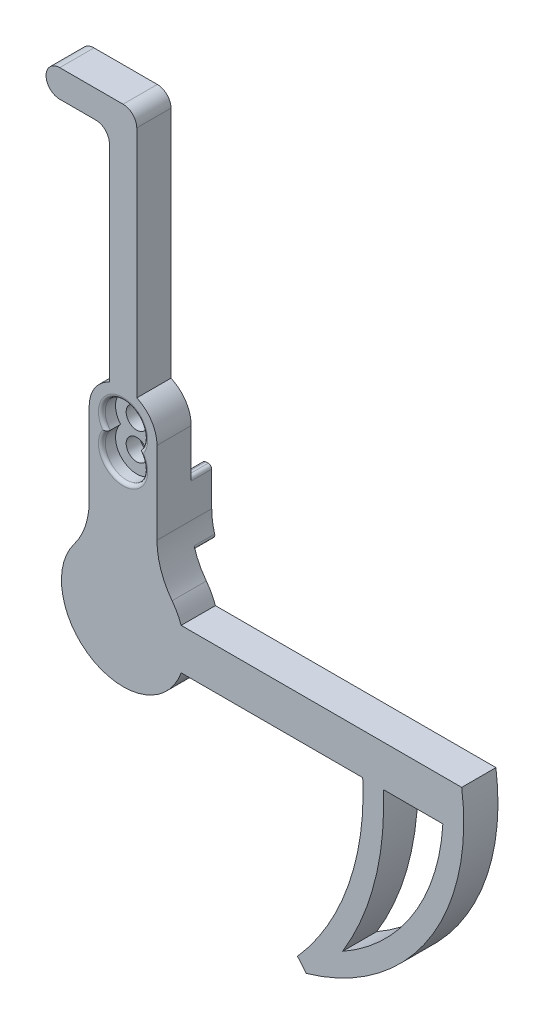
SolidWorks part; units mm, degrees
material "PLA"
ref_plane "Front Plane" through (0, 0, 0) normal (0, 0, 1) x (1, 0, 0)
ref_plane "Top Plane" through (0, 0, 0) normal (0, 1, 0) x (1, 0, 0)
ref_plane "Right Plane" through (0, 0, 0) normal (1, 0, 0) x (0, 0, -1)
sketch "Sketch1" plane through (0, 0, 0) normal (0, 0, 1) x (1, 0, 0)
  line L0 (-15.8075, -15.8075) -> (15.8075, 15.8075) construction
  line L1 (-15.8075, 15.8075) -> (15.8075, -15.8075) construction
  line L2 (0, 0) -> (0, 22.3552) construction
  line L3 (-3.5028, 12) -> (-3.35, 24)
  line L4 (-4.95, 12) -> (-4.95, 24)
  line L5 (4.95, 12) -> (4.95, 24)
  line L6 (3.5028, 12) -> (3.35, 24)
  line L9 (0.65, -3.8962) -> (0.65, -7.1706)
  line L10 (3.15, 12) -> (3.15, 24)
  line L11 (-3.15, 24) -> (-3.15, 12)
  line L12 (-0.65, -7.1706) -> (-0.65, -3.8962)
  line L13 (-0.65, 3.8962) -> (-0.65, 7.6481)
  line L14 (0.65, 7.6481) -> (0.65, 3.8962)
  line L15 (0.65, -3.8962) -> (0.65, -7.1706) construction
  line L16 (3.15, 12) -> (3.15, 24) construction
  line L17 (-3.15, 24) -> (-3.15, 12) construction
  line L18 (-0.65, -7.1706) -> (-0.65, -3.8962) construction
  line L19 (-0.65, 3.8962) -> (-0.65, 7.6481) construction
  line L20 (0.65, 7.6481) -> (0.65, 3.8962) construction
  circle A0 centre (0, 0) radius 22.3552 construction
  circle A1 centre (0, 20) radius 1.55
  circle A2 centre (0, 24) radius 1.55
  arc A3 (1.4948, 8.875) -> (-1.4948, 8.875) centre (0, 0) ccw
  circle A4 centre (-15.7528, 12) radius 12.25 construction
  arc A5 (-4.1855, 7.9675) -> (-3.5028, 12) centre (-15.7528, 12) ccw
  arc A6 (3.35, 24) -> (-3.35, 24) centre (0, 24) ccw
  circle A7 centre (-15.7528, 12) radius 10.8028 construction
  arc A9 (-4.95, 12) -> (-7.1593, 5.4538) centre (-15.7528, 12) cw
  arc A11 (-4.95, 24) -> (4.95, 24) centre (0, 24) cw
  arc A12 (0.65, -7.1706) -> (5.7275, 4.363) centre (0, 0) ccw
  arc A13 (3.15, 12) -> (5.7275, 4.363) centre (15.7528, 12) ccw
  arc A14 (3.15, 24) -> (-3.15, 24) centre (0, 24) ccw
  arc A15 (-5.7275, 4.363) -> (-3.15, 12) centre (-15.7528, 12) ccw
  arc A16 (-5.7275, 4.363) -> (-0.65, -7.1706) centre (0, 0) ccw
  arc A17 (-0.65, 3.8962) -> (-0.65, -3.8962) centre (0, 0) ccw
  arc A18 (0.65, 7.6481) -> (-0.65, 7.6481) centre (0, 9) ccw
  arc A19 (0.65, -3.8962) -> (0.65, 3.8962) centre (0, 0) ccw
  arc A20 (0.65, -7.1706) -> (5.7275, 4.363) centre (0, 0) ccw construction
  arc A21 (3.15, 12) -> (5.7275, 4.363) centre (15.7528, 12) ccw construction
  arc A22 (3.15, 24) -> (-3.15, 24) centre (0, 24) ccw construction
  arc A23 (-5.7275, 4.363) -> (-3.15, 12) centre (-15.7528, 12) ccw construction
  arc A24 (-5.7275, 4.363) -> (-0.65, -7.1706) centre (0, 0) ccw construction
  arc A25 (-0.65, 3.8962) -> (-0.65, -3.8962) centre (0, 0) ccw construction
  arc A26 (0.65, 7.6481) -> (-0.65, 7.6481) centre (0, 9) ccw construction
  arc A27 (0.65, -3.8962) -> (0.65, 3.8962) centre (0, 0) ccw construction
  arc A29 (-7.1593, 5.4538) -> (7.1593, 5.4538) centre (0, 0) ccw
  circle A30 centre (0, 0) radius 7.7902
  arc A31 (-4.1855, 7.9675) -> (-5.1734, 5.8243) centre (21.9382, -5.373) ccw
  arc A32 (4.1855, 7.9675) -> (5.1734, 5.8243) centre (-21.9382, -5.373) cw
  arc A33 (4.1855, 7.9675) -> (3.5028, 12) centre (15.7528, 12) cw
  arc A34 (4.95, 12) -> (7.1593, 5.4538) centre (15.7528, 12) ccw
  dimension "D1" = 3.1
  dimension "D2" = 3.1
  dimension "D6" = 18
  dimension "D8" = 24.5
  dimension "D9" = 15.5803
  dimension "D3" = 4
  dimension "D4" = 20
  dimension "D5" = 45
  dimension "D7" = 0
extrude "Boss-Extrude1" add sketch "Sketch1" along normal blind 4 contours A2 | A1 | A9 A29 A34 L5 A11 L4 region at (0, 20, 0) region at (0, 24, 0)
extrude "Boss-Extrude2" add sketch "Sketch1<6>" against normal blind 1 contours A9 A29 A34 L5 A11 L4 A33 A32 A30 A31 A5 L3 A6 L6 region at (-4.53, 18, 0)
sketch "Sketch1<6>" plane through (0, 0, 0) normal (0, 0, 1) x (1, 0, 0) same geometry as "Sketch1"
sketch "Sketch2" plane through (0, 0, -1) normal (0, 0, -1) x (-1, 0, 0)
  line L0 (3.583, 17.483) -> (3.6529, 11.9938)
  line L1 (0, 0) -> (0, 24) construction
  line L2 (4.95, 12) -> (4.95, 24)
  line L3 (-4.95, 24) -> (-4.95, 12)
  line L4 (4.95, 12) -> (4.95, 24)
  line L5 (-4.95, 24) -> (-4.95, 12)
  line L6 (3.5028, 12) -> (3.35, 24)
  line L7 (-3.35, 24) -> (-3.5028, 12)
  line L8 (3.5028, 12) -> (3.35, 24) construction
  line L9 (-3.35, 24) -> (-3.5028, 12) construction
  line L10 (4.95, 17.5004) -> (3.583, 17.483)
  line L11 (4.2882, 8.1307) -> (5.5172, 8.5455)
  line L12 (-3.583, 17.483) -> (-3.6529, 11.9938)
  line L13 (-4.95, 17.5004) -> (-3.583, 17.483)
  line L14 (-4.2882, 8.1307) -> (-5.5172, 8.5455)
  circle A0 centre (15.7528, 12) radius 12.0999 construction
  arc A1 (4.2882, 8.1307) -> (3.6529, 11.9938) centre (15.7528, 12) cw
  arc A2 (-4.2882, 8.1307) -> (-3.6529, 11.9938) centre (-15.7528, 12) ccw
  arc A4 (4.95, 12) -> (7.1593, 5.4538) centre (15.7528, 12) ccw
  arc A5 (4.95, 24) -> (-4.95, 24) centre (0, 24) ccw
  arc A6 (-7.1593, 5.4538) -> (-4.95, 12) centre (-15.7528, 12) ccw
  arc A7 (-7.1593, 5.4538) -> (7.1593, 5.4538) centre (0, 0) ccw
  arc A8 (4.95, 12) -> (7.1593, 5.4538) centre (15.7528, 12) ccw
  arc A9 (4.95, 24) -> (-4.95, 24) centre (0, 24) ccw
  arc A10 (-7.1593, 5.4538) -> (-4.95, 12) centre (-15.7528, 12) ccw
  arc A11 (-7.1593, 5.4538) -> (7.1593, 5.4538) centre (0, 0) ccw
  arc A14 (-4.1855, 7.9675) -> (-3.5028, 12) centre (-15.7528, 12) ccw
  arc A15 (-4.1855, 7.9675) -> (-5.1734, 5.8243) centre (21.9382, -5.373) ccw
  arc A16 (-5.1734, 5.8243) -> (5.1734, 5.8243) centre (0, 0) ccw
  arc A17 (5.1734, 5.8243) -> (4.1855, 7.9675) centre (-21.9382, -5.373) ccw
  arc A18 (3.5028, 12) -> (4.1855, 7.9675) centre (15.7528, 12) ccw
  arc A19 (3.35, 24) -> (-3.35, 24) centre (0, 24) ccw
  arc A20 (-4.1855, 7.9675) -> (-3.5028, 12) centre (-15.7528, 12) ccw construction
  arc A21 (-4.1855, 7.9675) -> (-5.1734, 5.8243) centre (21.9382, -5.373) ccw construction
  arc A22 (-5.1734, 5.8243) -> (5.1734, 5.8243) centre (0, 0) ccw construction
  arc A23 (5.1734, 5.8243) -> (4.1855, 7.9675) centre (-21.9382, -5.373) ccw construction
  arc A24 (3.5028, 12) -> (4.1855, 7.9675) centre (15.7528, 12) ccw construction
  arc A25 (3.35, 24) -> (-3.35, 24) centre (0, 24) ccw construction
  arc M20 (7.1593, 5.4538) -> (4.95, 12) centre (15.7528, 12) cw
  line M21 (4.95, 12) -> (4.95, 24)
  arc M24 (-4.95, 12) -> (-7.1593, 5.4538) centre (-15.7528, 12) cw
  dimension "D3" = 0.15
  dimension "D4" = 5.5
  dimension "D1" = 0
  dimension "D2" = 0
extrude "Boss-Extrude3" add sketch "Sketch2" along normal blind 3 contours A1 L11 L10 L0 M20 M21 | L14 A2 L12 L13 L5 M24 region at (-4.3663, 12.9319, -1) region at (4.3663, 12.9319, -1)
sketch "Sketch3" plane through (0, 0, 4) normal (0, 0, 1) x (1, 0, 0)
  circle A0 centre (0, 24) radius 1.55 construction
  circle A1 centre (0, 20) radius 1.55 construction
  circle A2 centre (0, 24) radius 1.55
  circle A3 centre (0, 20) radius 1.55
  circle A4 centre (0, 20) radius 3.1
  circle A5 centre (0, 24) radius 3.1
  dimension "D1" = 6.2
  dimension "D2" = 6.2
extrude "Cut-Extrude1" cut sketch "Sketch3" against normal blind 2
fillet "Fillet2" radius 0.5 10 edges at (-3.583, 17.483, -2.5) (-4.95, 17.5004, -2.5) (3.583, 17.483, -2.5) (-5.5172, 8.5455, -2.5) (-4.2882, 8.1307, -2.5) (4.95, 17.5004, -2.5) (5.5172, 8.5455, -2.5) (4.2882, 8.1307, -2.5) (0, 27.1, 4) (0, 16.9, 4)
ref_plane "Plane1" through (0, 0, 5) normal (0, 0, 1) x (1, 0, 0)
sketch "Sketch4" plane through (0, 0, 4) normal (0, 0, 1) x (1, 0, 0)
  line L0 (0, 0) -> (34.7263, 0) construction
  line L1 (0, 0) -> (25.4725, -30.357) construction
  line L2 (25.4725, -30.357) -> (26.7581, -31.8891)
  line L3 (34.7263, 0) -> (49.7263, 0)
  line L4 (35, -3) -> (8.4853, -3)
  line L5 (35, 3) -> (8.4853, 3)
  line L6 (35, 3) -> (49.7263, 3)
  line L7 (49.7263, 3) -> (49.7263, 0)
  line L9 (38.0037, -3) -> (46.7056, -3)
  circle A0 centre (0, 0) radius 9
  arc A3 (34.7263, 0) -> (25.4725, -30.357) centre (-3.3379, -4.9858) cw
  arc A4 (49.7263, 0) -> (26.7581, -31.8891) centre (17.9508, -1.3297) cw
  circle A5 centre (17.9508, -1.3297) radius 31.8032 construction
  arc A6 (49.7263, 0) -> (49.458, 3) centre (17.9508, -1.3297) ccw
  circle A7 centre (17.9508, -1.3297) radius 28.8032 construction
  circle A8 centre (-3.3379, -4.9858) radius 41.3893 construction
  arc A9 (38.0037, -3) -> (32.0548, -26.4435) centre (-3.3379, -4.9858) cw
  arc A10 (46.7056, -3) -> (32.0548, -26.4435) centre (17.9508, -1.3297) cw
  point P20 (32.0548, -26.4435)
  arc M20 (-7.1593, 5.4538) -> (7.1593, 5.4538) centre (0, 0) ccw
  dimension "D1" = 18
  dimension "D2" = 35
  dimension "D4" = 6
  dimension "D8" = 18
  dimension "D9" = 3
  dimension "D10" = 3
  dimension "D3" = 2
  dimension "D5" = 15
  dimension "D6" = 50
  dimension "D7" = 3
extrude "Boss-Extrude4" add sketch "Sketch4" against normal up to surface (5 mm away) contours A3 L3 L7 L6 L5 L4 M20 | L3 A3 L2 L9 region at (33.2943, -17.7435, 4) region at (26.3516, 0.3286, 4) up to face at (0, 12.7161, -1)
sketch "Sketch5" plane through (0, 0, 4) normal (0, 0, 1) x (1, 0, 0)
  line L0 (0, 0) -> (0, 62.6797) construction
  line L1 (0, 0) -> (-32.3114, 53.7096) construction
  line L8 (0, 62.6797) -> (-11.25, 62.6797) construction
  line L9 (-11.25, 60.6797) -> (-11.25, 64.6797)
  line L10 (-11.25, 64.6797) -> (2, 64.6797)
  line L11 (2, 64.6797) -> (2, 28.528)
  line L12 (-11.25, 60.6797) -> (2, 60.6797)
  line L13 (-2, 64.6797) -> (-2, 28.528)
  arc A2 (4.95, 24) -> (-4.95, 24) centre (0, 24) ccw construction
  arc A3 (-2, 28.528) -> (2, 28.528) centre (0, 24) cw
  arc M19 (4.95, 24) -> (-4.95, 24) centre (0, 24) ccw
  dimension "D1" = 62.6797
  dimension "D2" = 11.25
  dimension "D3" = 2
  dimension "D4" = 2
extrude "Boss-Extrude5" add sketch "Sketch5" against normal up to surface (5 mm away) contours L12 L13 L11 M19 | L10 L13 L12 L11 | L13 L10 L9 L12 region at (-6.625, 62.6797, 4) region at (0, 62.6797, 4) region at (0, 44.7455, 4) up to face at (5.6426, 7.7752, -1)
fillet "Fillet3" radius 2 4 edges at (-2, 60.6797, 1.5) (-11.25, 60.6797, 1.5) (-11.25, 64.6797, 1.5) (2, 64.6797, 1.5)
equation "\"O_R\"= 4'Outer radius (Addendum)"
equation "\"I_R\"= 2.9'Inner radius (Dedendum)"
equation "\"N\"= 25'# of teeth"
equation "\"phi\"= 20'Pressure angle"
equation "\"P_R\"= 3'Pitch radius"
equation "\"a\"= ( \"period\" - ( \"err\" + \"T_F\" ) * ( \"I_R\" ) ) / ( 1 + ( \"O_R\" / \"I_R\" ) )'Outer arc degree"
equation "\"a_i\"= \"a\" * \"O_R\" / \"I_R\"'Inner arc degree (+manufacturing)"
equation "\"err\"= .03'Manufacturing error"
equation "\"period\"= 360 / \"N\"'Period of gear teeth"
equation "\"T_F\"= \"O_R\" / 2cm'Transition factor for curve"
equation "\"D4@Sketch19\"= \"a_i\" / 2"
